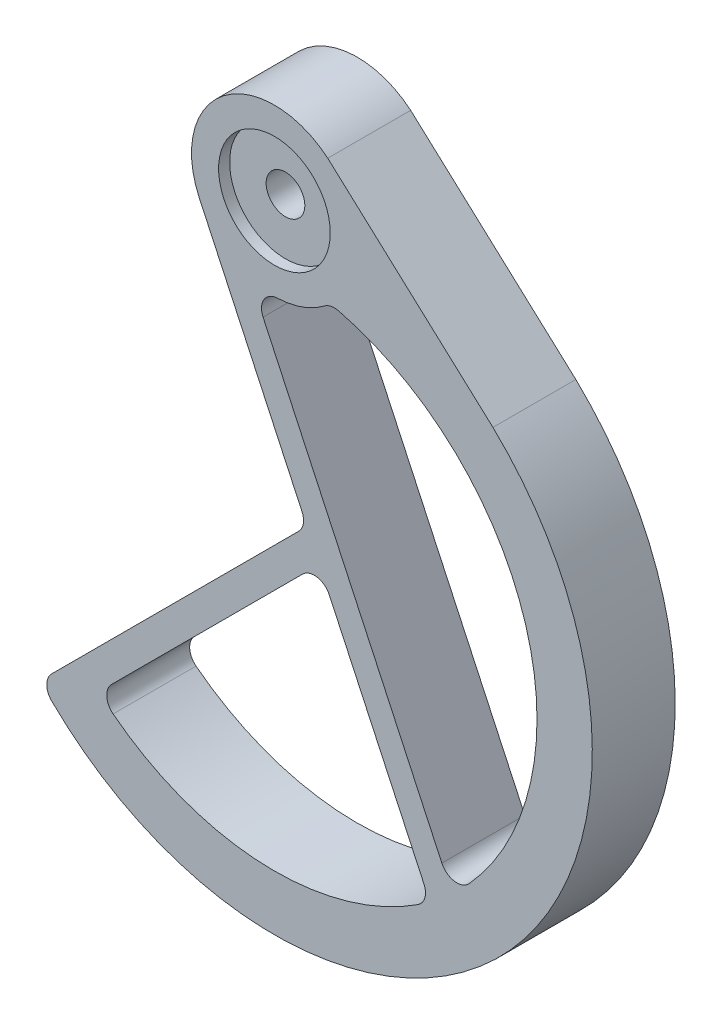
SolidWorks part; units mm, degrees
material "ABS"
ref_plane "正面" through (0, 0, 0) normal (0, 0, 1) x (1, 0, 0)
ref_plane "平面" through (0, 0, 0) normal (0, 1, 0) x (1, 0, 0)
ref_plane "右側面" through (0, 0, 0) normal (1, 0, 0) x (0, 0, -1)
sketch "ｽｹｯﾁ1" plane through (0, 0, 0) normal (0, 0, 1) x (1, 0, 0)
  line L1 (9.9336, 0.7043) -> (27.0462, -35.9938)
  line L2 (9.6418, 68.9907) -> (39.5241, 41.7624)
  line L4 (4.3888, 7.9244) -> (-40.3035, -36.7679)
  line L5 (5.0933, 1.5578) -> (-29.4572, -32.9928)
  line L6 (-13.5946, 51.1607) -> (4.9864, 11.3135)
  line L7 (30.2877, -31.1143) -> (-2.0547, 38.2444)
  arc A0 (-40.2839, -41.0299) -> (37.9168, 43.2269) centre (0, 0) ccw
  arc A1 (-29.1788, -37.4813) -> (25.9673, -39.7737) centre (0, 0) ccw
  arc A2 (0.5535, 42.5102) -> (9.0577, 45.5435) centre (0, 57.5) ccw
  arc A3 (35.2318, -31.8586) -> (11.602, 46.0613) centre (0, 0) ccw
  arc A4 (10.5469, 68.1659) -> (-13.5946, 51.1607) centre (0, 57.5) ccw
  arc A5 (-40.3035, -36.7679) -> (-40.2839, -41.0299) centre (-38.1821, -38.8893) ccw
  arc A6 (-29.4572, -32.9928) -> (-29.1788, -37.4813) centre (-27.3359, -35.1141) ccw
  arc A7 (27.0462, -35.9938) -> (25.9673, -39.7737) centre (24.3273, -37.2617) cw
  arc A8 (5.0933, 1.5578) -> (9.9336, 0.7043) centre (7.2147, -0.5635) cw
  arc A9 (35.2318, -31.8586) -> (30.2877, -31.1143) centre (33.0067, -29.8464) cw
  arc A10 (4.9864, 11.3135) -> (4.3888, 7.9244) centre (2.2675, 10.0457) cw
  arc A11 (-2.0547, 38.2444) -> (0.5535, 42.5102) centre (0.6642, 39.5123) cw
  arc A12 (11.602, 46.0613) -> (9.0577, 45.5435) centre (10.8692, 43.1522) ccw
  point P24 (8.1229, 4.5874)
  dimension "D1" = 3
  dimension "D2" = 3
  dimension "D3" = 3
  dimension "D4" = 3
  dimension "D5" = 3
  dimension "D6" = 3
  dimension "D7" = 3
  dimension "D8" = 3
extrude "ﾎﾞｽ - 押し出し1" add sketch "ｽｹｯﾁ1" along normal blind 15 contours L6 A10 L4 A5 A0 L2 A4 A12 A3 A9 L7 A11 A2 L5 A8 L1 A7 A1 A6 region at (8.9951, 67.3719, 0)
sketch "ｽｹｯﾁ6" plane through (0, 0, 15) normal (0, 0, 1) x (1, 0, 0)
  circle A0 centre (0, 57.5) radius 3.5
extrude "ｶｯﾄ - 押し出し2" cut sketch "ｽｹｯﾁ6" against normal blind 15
sketch "ｽｹｯﾁ7" plane through (0, 0, 15) normal (0, 0, 1) x (1, 0, 0)
  circle A0 centre (0, 57.5) radius 10.1
extrude "ｶｯﾄ - 押し出し3" cut sketch "ｽｹｯﾁ7" against normal blind 2
